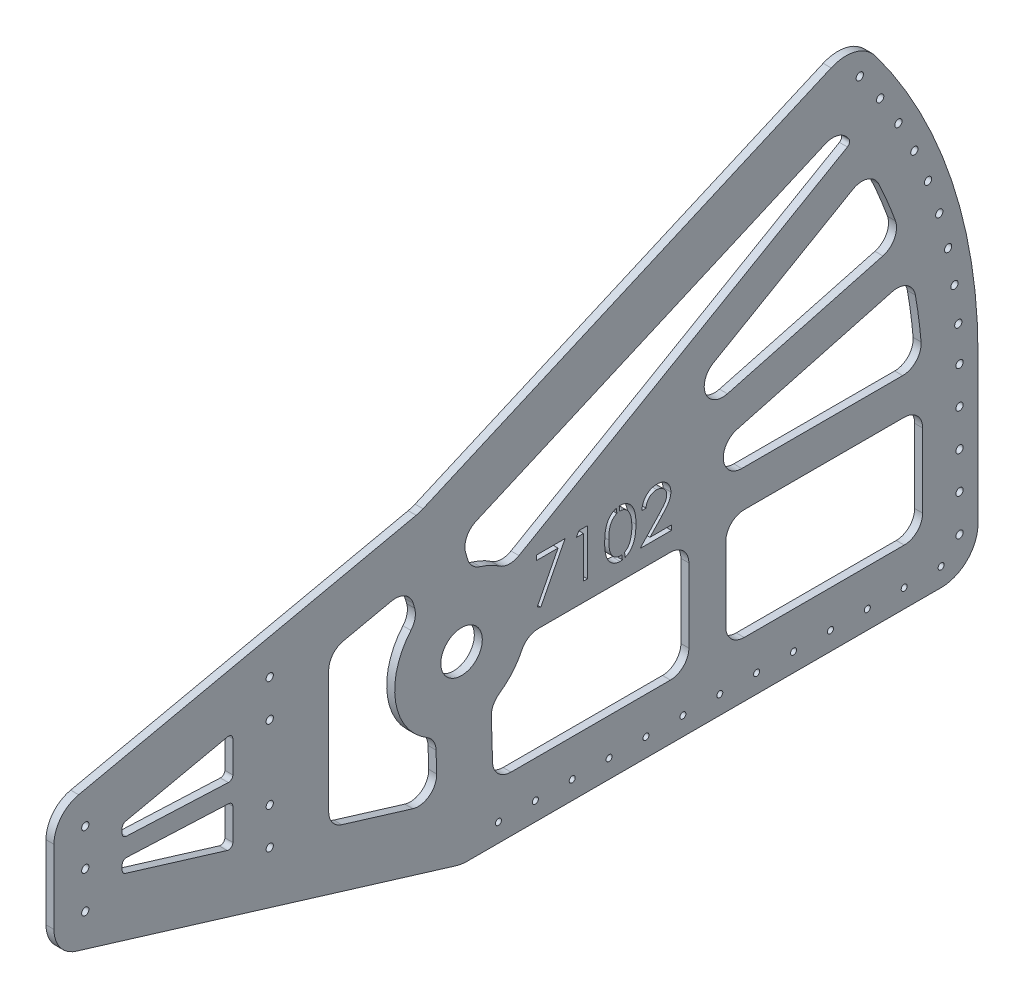
SolidWorks part; units mm, degrees
ref_plane "Front Plane" through (0, 0, 0) normal (0, 0, 1) x (1, 0, 0)
ref_plane "Top Plane" through (0, 0, 0) normal (0, 1, 0) x (1, 0, 0)
ref_plane "Right Plane" through (0, 0, 0) normal (1, 0, 0) x (0, 0, -1)
sketch "Sketch1" plane through (0, 0, 0) normal (1, 0, 0) x (0, 0, -1)
  line L0 (0, 0) -> (-195.58, 0) construction
  line L1 (7.3323, 0) -> (3.6662, 6.35) construction
  line L2 (3.6662, 6.35) -> (-3.6662, 6.35) construction
  line L3 (-3.6662, 6.35) -> (-7.3323, 0) construction
  line L4 (-7.3323, 0) -> (-3.6662, -6.35) construction
  line L5 (-3.6662, -6.35) -> (3.6662, -6.35) construction
  line L6 (3.6662, -6.35) -> (7.3323, 0) construction
  line L7 (0, -101.6) -> (0, -127) construction
  line L8 (-208.6619, 44.2059) -> (-28.8306, 97.4236)
  line L9 (0, -127) -> (-212.5477, -42.8649)
  line L10 (0, -127) -> (355.6, -127)
  line L11 (-28.8306, 97.4236) -> (272.3847, 228.6)
  line L12 (355.6, 0) -> (355.6, -127)
  circle A0 centre (0, 0) radius 76.2 construction
  circle A1 centre (0, 0) radius 14.2875
  circle A2 centre (0, 0) radius 6.35 construction
  circle A3 centre (0, 0) radius 33.4264 construction
  circle A4 centre (-195.58, 0) radius 9.906
  circle A5 centre (-195.58, 0) radius 25.4 construction
  circle A6 centre (-195.58, 25.4) radius 3.9687
  circle A7 centre (-170.18, 0) radius 3.9687
  circle A8 centre (-195.58, -25.4) radius 3.9688
  circle A9 centre (-220.98, 0) radius 3.9687
  circle A10 centre (-195.58, 0) radius 33.401 construction
  circle A11 centre (0, 0) radius 101.6
  circle A12 centre (-195.58, 0) radius 46.101
  circle A13 centre (215.9, 0) radius 114.3 construction
  arc A14 (304.8, -127) -> (248.0181, 217.9886) centre (0, 0) ccw
  arc A15 (355.6, 0) -> (272.3847, 228.6) centre (0, 0) ccw
  arc A16 (272.3847, 228.6) -> (332.1481, -127) centre (0, 0) ccw construction
  circle A17 centre (0, 0) radius 355.6 construction
  arc A18 (248.0181, 217.9886) -> (304.8, -127) centre (0, 0) ccw construction
  circle A19 centre (0, 0) radius 330.2 construction
  arc A22 (318.5144, -127) -> (260.2228, 223.3036) centre (0, 0) ccw
  arc A23 (260.2228, 223.3036) -> (318.5144, -127) centre (0, 0) ccw construction
  arc A24 (332.1481, -127) -> (355.6, 0) centre (0, 0) ccw construction
  point P26 (-195.58, 0)
  dimension "D1" = 152.4
  dimension "D2" = 28.575
  dimension "D4" = 66.8528
  dimension "D5" = 19.812
  dimension "D6" = 50.8
  dimension "D7" = 7.9375
  dimension "D11" = 66.802
  dimension "D14" = 228.6
  dimension "D17" = 355.6
  dimension "D18" = 25.4
  dimension "D19" = 685.8
  dimension "D3" = 12.7
  dimension "D9" = 195.58
  dimension "D13" = 25.4
  dimension "D16" = 355.6
  dimension "D10" = 25.4
  dimension "D12" = 12.7
  dimension "D15" = 25.4
  dimension "D8" = 4
extrude "Boss-Extrude1" add sketch "Sketch1" along normal mid plane 5.5 contours A12 A4 A6 A7 A8 A9 | A11 A1 | L10 A14 L11 A11 L8 A12 L9 | L10 A22 L11 A14 | A22 L10 L12 A15 L11 region at (0, 79.0972, -59.0807) region at (0, 18.9853, -149.0281) region at (0, 35.8903, 168.7722) region at (0, 217.3187, -255.5695) region at (0, 222.5763, -267.7737)
sketch "Sketch2" plane through (2.75, 0, 0) normal (1, 0, 0) x (0, 0, -1)
  line L0 (355.6, -114.3) -> (-32.0836, -114.3) construction
  line L1 (355.6, 0) -> (355.6, -127) construction
  line L2 (0, -127) -> (-212.5477, -42.8649) construction
  line L3 (0, -127) -> (355.6, -127) construction
  circle A0 centre (330.2, -114.3) radius 2.07
  circle A1 centre (304.8, -114.3) radius 2.07
  circle A2 centre (279.4, -114.3) radius 2.07
  circle A3 centre (254, -114.3) radius 2.07
  circle A4 centre (228.6, -114.3) radius 2.07
  circle A5 centre (203.2, -114.3) radius 2.07
  circle A6 centre (177.8, -114.3) radius 2.07
  circle A7 centre (152.4, -114.3) radius 2.07
  circle A8 centre (127, -114.3) radius 2.07
  circle A9 centre (101.6, -114.3) radius 2.07
  circle A10 centre (76.2, -114.3) radius 2.07
  circle A11 centre (50.8, -114.3) radius 2.07
  circle A12 centre (25.4, -114.3) radius 2.07
  dimension "D2" = 4.14
  dimension "D1" = 12.7
  dimension "D3" = 25.4
  dimension "D5" = 25.4
  dimension "D4" = 13
extrude "Cut-Extrude1" cut sketch "Sketch2" against normal up to next
sketch "Sketch3" plane through (2.75, 0, 0) normal (1, 0, 0) x (0, 0, -1)
  line L0 (342.9, 0) -> (342.9, -127) construction
  line L1 (0, -127) -> (355.6, -127) construction
  line L2 (0, 0) -> (342.9, 0) construction
  line L3 (0, 0) -> (342.0224, 24.5165) construction
  arc A0 (318.5144, -127) -> (260.2228, 223.3036) centre (0, 0) ccw construction
  arc A1 (342.9, 0) -> (260.2228, 223.3036) centre (0, 0) ccw construction
  arc A2 (318.5144, -127) -> (342.9, 0) centre (0, 0) ccw construction
  circle A3 centre (342.9, 0) radius 2.5
  circle A4 centre (342.0224, 24.5165) radius 2.5
  circle A5 centre (339.3943, 48.9075) radius 2.5
  circle A6 centre (335.0289, 73.0481) radius 2.5
  circle A7 centre (328.9488, 96.8149) radius 2.5
  circle A8 centre (321.1849, 120.0861) radius 2.5
  circle A9 centre (311.7771, 142.7427) radius 2.5
  circle A10 centre (300.7734, 164.6686) radius 2.5
  circle A11 centre (288.2303, 185.7517) radius 2.5
  circle A12 centre (274.2119, 205.8841) radius 2.5
  circle A13 centre (330.2, -114.3) radius 2.07 construction
  circle A14 centre (342.9, -25.4) radius 2.5
  circle A15 centre (342.9, -50.8) radius 2.5
  circle A16 centre (342.9, -76.2) radius 2.5
  circle A17 centre (342.9, -101.6) radius 2.5
  point P9 (0, 0)
  dimension "D1" = 5
  dimension "D3" = 342.9
  dimension "D4" = 4.1
  dimension "D6" = 25.4
  dimension "D5" = 5
  dimension "D2" = 10
extrude "Cut-Extrude2" cut sketch "Sketch3" against normal up to next
sketch "Sketch4" plane through (2.75, 0, 0) normal (1, 0, 0) x (0, 0, -1)
  line L0 (0, 0) -> (-195.58, 0) construction
  line L1 (0, 0) -> (-149.479, 0) construction
  line L2 (-195.58, 0) -> (-195.58, -49.5814) construction
  line L3 (0, -127) -> (-212.5477, -42.8649) construction
  line L4 (-280.63, 25.4) -> (-280.63, -25.4)
  line L5 (-265.3704, -46.0115) -> (0, -127)
  line L6 (-195.58, -49.5814) -> (-212.5477, -42.8649)
  line L7 (-263.6507, 46.4597) -> (-28.8306, 97.4236)
  line L8 (-208.6619, 44.2059) -> (-28.8306, 97.4236) construction
  line L9 (-208.6619, 44.2059) -> (-28.8306, 97.4236)
  line L10 (-149.479, 0) -> (-195.58, 0) construction
  line L11 (0, -127) -> (-195.58, -49.5814)
  circle A0 centre (-132.08, 25.4) radius 2.5
  circle A1 centre (-132.08, -25.4) radius 2.5
  circle A2 centre (-132.08, 0) radius 2.5
  circle A3 centre (-259.08, -25.4) radius 2.5
  circle A4 centre (-259.08, 0) radius 2.5
  circle A5 centre (-259.08, 25.4) radius 2.5
  arc A6 (-280.63, 25.4) -> (-263.6507, 46.4597) centre (-259.08, 25.4) cw
  arc A7 (-280.63, -25.4) -> (-265.3704, -46.0115) centre (-259.08, -25.4) ccw
  circle A8 centre (-195.58, 0) radius 46.101 construction
  arc A9 (-208.6619, 44.2059) -> (-212.5477, -42.8649) centre (-195.58, 0) ccw
  arc A10 (-149.479, 0) -> (-208.6619, 44.2059) centre (-195.58, 0) ccw construction
  arc A11 (-195.58, -46.101) -> (-149.479, 0) centre (-195.58, 0) ccw construction
  arc A12 (-212.5477, -42.8649) -> (-195.58, -46.101) centre (-195.58, 0) ccw construction
  arc A13 (-263.6507, 46.4597) -> (-280.63, 25.4) centre (-259.08, 25.4) cw construction
  circle A14 centre (-259.08, 25.4) radius 21.55 construction
  arc A15 (-265.3704, -46.0115) -> (-280.63, -25.4) centre (-259.08, -25.4) ccw construction
  circle A16 centre (-259.08, -25.4) radius 21.55 construction
  dimension "D1" = 5
  dimension "D2" = 25.4
  dimension "D3" = 63.5
  dimension "D4" = 19.05
extrude "Boss-Extrude2" add sketch "Sketch4" against normal up to surface (5.5 mm away) up to face at (-2.75, 24.5165, -344.5224)
extrude "Cut-Extrude3" cut sketch "Sketch4<2>" against normal up to next contours A0 | A1
sketch "Sketch4<2>" plane through (2.75, 0, 0) normal (1, 0, 0) x (0, 0, -1) same geometry as "Sketch4"
sketch "Sketch5" plane through (2.75, 0, 0) normal (1, 0, 0) x (0, 0, -1)
  line L0 (-132.08, 75.015) -> (-132.08, -86.6904) construction
  line L1 (-28.8306, 97.4236) -> (-263.6507, 46.4597) construction
  line L2 (-265.3704, -46.0115) -> (0, -127) construction
  line L3 (0, 0) -> (-195.58, 0) construction
  line L4 (0, 0) -> (-195.58, 0) construction
  circle A1 centre (-132.08, 25.4) radius 2.5 construction
  circle A2 centre (-132.08, 25.4) radius 2.5 construction
  circle A3 centre (-132.08, 50.8) radius 2.5
  circle A4 centre (-132.08, -50.8) radius 2.5
  dimension "D1" = 50.8
extrude "Cut-Extrude4" cut sketch "Sketch5" against normal up to next
fillet "Fillet1" radius 25.4 4 edges at (0, -127, 0) (0, -127, -355.6) (0, 228.6, -272.3847) (0, 97.4236, 28.8306)
sketch "Sketch9" plane through (2.75, 0, 0) normal (1, 0, 0) x (0, 0, -1)
  line L0 (-91.48, 50.8) -> (-91.48, -50.8)
  line L1 (-26.5293, 98.4258) -> (254.4732, 220.7998) construction
  line L2 (355.6, 0) -> (355.6, -101.6) construction
  line L3 (3.7896, -127) -> (330.2, -127) construction
  line L4 (-265.3704, -46.0115) -> (-3.6246, -125.8938) construction
  line L5 (-280.63, 25.4) -> (-280.63, -25.4) construction
  line L6 (-31.2836, 96.8912) -> (-263.6507, 46.4597) construction
  line L7 (355.6, 0) -> (355.6, -101.6)
  line L8 (3.7896, -127) -> (330.2, -127)
  line L9 (-265.3704, -46.0115) -> (-3.6246, -125.8938)
  line L10 (-280.63, 25.4) -> (-280.63, -25.4)
  line L11 (-31.2836, 96.8912) -> (-263.6507, 46.4597)
  line L12 (-26.5293, 98.4258) -> (254.4732, 220.7998)
  line L13 (0, 0) -> (-28.8687, 97.5413) construction
  line L14 (0, 0) -> (3.7896, -127) construction
  line L15 (18.9678, 3.0375) -> (22.8481, -127)
  line L16 (18.9678, 3.0375) -> (-11.2349, 105.0864)
  line L17 (-18.9678, -3.0375) -> (-15.2519, -127.5682)
  line L18 (-6.3726, -45.5943) -> (-47.5013, 93.3714)
  line L19 (-18.9678, -3.0375) -> (-47.1354, 92.135) construction
  line L20 (18.9678, 3.0375) -> (-10.6019, 102.9476) construction
  line L21 (18.9678, 3.0375) -> (22.8312, -126.4318) construction
  line L22 (-23.2028, 59.658) -> (-242.53, 12.0566)
  line L23 (-242.53, 12.0566) -> (-242.53, -13.1473)
  line L24 (-242.53, -13.1473) -> (5.6845, -88.9)
  line L25 (5.6845, -88.9) -> (317.5, -88.9)
  line L26 (317.5, 0) -> (317.5, -88.9)
  line L27 (-11.3171, 63.4945) -> (260.3085, 181.7848)
  circle A0 centre (-132.08, -50.8) radius 2.5 construction
  circle A1 centre (-132.08, 50.8) radius 2.5 construction
  circle A2 centre (0, 0) radius 46.0375
  circle A3 centre (0, 0) radius 46.0375
  circle A13 centre (-132.08, -50.8) radius 2.5
  circle A14 centre (-132.08, 50.8) radius 2.5
  circle A15 centre (-132.08, -50.8) radius 40.6
  circle A16 centre (-132.08, 50.8) radius 40.6
  arc A17 (284.9697, 212.7055) -> (254.4732, 220.7998) centre (264.6148, 197.5122) ccw construction
  arc A18 (355.6, 0) -> (284.9697, 212.7055) centre (0, 0) ccw construction
  arc A19 (330.2, -127) -> (355.6, -101.6) centre (330.2, -101.6) ccw construction
  arc A20 (-3.6246, -125.8938) -> (3.7896, -127) centre (3.7896, -101.6) ccw construction
  arc A21 (-280.63, -25.4) -> (-265.3704, -46.0115) centre (-259.08, -25.4) ccw construction
  arc A22 (-263.6507, 46.4597) -> (-280.63, 25.4) centre (-259.08, 25.4) ccw construction
  arc A23 (-31.2836, 96.8912) -> (-26.5293, 98.4258) centre (-36.6708, 121.7133) ccw construction
  arc A24 (284.9697, 212.7055) -> (254.4732, 220.7998) centre (264.6148, 197.5122) ccw
  arc A25 (355.6, 0) -> (284.9697, 212.7055) centre (0, 0) ccw
  arc A26 (330.2, -127) -> (355.6, -101.6) centre (330.2, -101.6) ccw
  arc A27 (-3.6246, -125.8938) -> (3.7896, -127) centre (3.7896, -101.6) ccw
  arc A28 (-280.63, -25.4) -> (-265.3704, -46.0115) centre (-259.08, -25.4) ccw
  arc A29 (-263.6507, 46.4597) -> (-280.63, 25.4) centre (-259.08, 25.4) ccw
  arc A30 (-31.2836, 96.8912) -> (-26.5293, 98.4258) centre (-36.6708, 121.7133) ccw
  arc A31 (-242.53, 12.0566) -> (-242.53, 12.0566) centre (-242.53, 12.0566) ccw
  arc A32 (-242.53, -13.1473) -> (-242.53, -13.1473) centre (-242.53, -13.1473) ccw
  arc A33 (5.6845, -88.9) -> (5.6845, -88.9) centre (5.6845, -88.9) ccw
  arc A34 (317.5, -88.9) -> (317.5, -88.9) centre (317.5, -88.9) ccw
  arc A35 (317.5, 0) -> (260.3085, 181.7848) centre (0, 0) ccw
  arc A36 (260.3085, 181.7848) -> (260.3085, 181.7848) centre (260.3085, 181.7848) ccw
  arc A37 (-23.2028, 59.658) -> (-11.3171, 63.4945) centre (-36.6708, 121.7133) ccw
  dimension "D1" = 31.75
  dimension "D2" = 38.1
  dimension "D3" = 19.05
  dimension "D4" = 19.05
  dimension "D5" = 38.1
extrude "Cut-Extrude7" cut sketch "Sketch9" against normal through all contours A16 L0 A15 L24 L17 A3 L18 L22 | A35 A36 L27 L16 A3 L15 L25 A34 L26 region at (2.75, -14.028, 59.5734) region at (2.75, 23.1221, -177.6674)
fillet "Fillet2" radius 12.7 12 edges at (0, -88.9, -317.5) (0, -88.9, -21.7112) (0, -41.3244, -20.2916) (0, 45.5943, -6.3726) (0, 68.2749, 0.34) (0, 181.7848, -260.3085) (0, 44.8396, 91.48) (0, 56.7376, 36.6591) (0, 34.7817, 30.1609) (0, -42.4607, 17.7915) (0, -82.0963, 16.6088) (0, -58.9915, 92.315)
sketch "Sketch10" plane through (2.75, 0, 0) normal (1, 0, 0) x (0, 0, -1)
  line L0 (0, 0) -> (274.9631, 158.75) construction
  line L1 (0, 0) -> (317.5, 0) construction
  line L2 (317.5, 0) -> (317.5, -76.2) construction
  line L4 (0, 0) -> (306.6814, 82.175) construction
  line L5 (6.35, -10.9985) -> (281.3131, 147.7515)
  line L6 (0, -12.7) -> (317.5, -12.7)
  line L7 (3.287, -12.2673) -> (309.9685, 69.9078)
  line L8 (-6.35, 10.9985) -> (268.6131, 169.7485)
  line L9 (0, 12.7) -> (317.5, 12.7)
  line L10 (-3.287, 12.2673) -> (303.3944, 94.4423)
  line L11 (20.9295, -62.7028) -> (317.5, -62.7028) construction
  line L12 (20.5155, -48.8267) -> (21.3436, -76.5788) construction
  line L13 (169.2148, -88.9) -> (169.2148, -12.7) construction
  line L15 (181.9148, -88.9) -> (181.9148, -12.7)
  line L16 (156.5148, -88.9) -> (156.5148, -12.7)
  line L17 (34.0379, -88.9) -> (304.8, -88.9) construction
  line L18 (4.2425, 52.7914) -> (2.8461, 57.5095) construction
  line L19 (9.9532, 72.7575) -> (250.6127, 177.5624) construction
  line L20 (317.5, 0) -> (317.5, -76.2)
  line L21 (34.0379, -88.9) -> (304.8, -88.9)
  line L22 (20.5155, -48.8267) -> (21.3436, -76.5788)
  line L23 (4.2425, 52.7914) -> (2.8461, 57.5095)
  line L24 (9.9532, 72.7575) -> (250.6127, 177.5624)
  arc A1 (317.5, 0) -> (266.337, 172.8319) centre (0, 0) ccw construction
  arc A2 (266.337, 172.8319) -> (250.6127, 177.5624) centre (255.6835, 165.9186) ccw construction
  arc A3 (304.8, -88.9) -> (317.5, -76.2) centre (304.8, -76.2) ccw construction
  arc A4 (21.3436, -76.5788) -> (34.0379, -88.9) centre (34.0379, -76.2) ccw construction
  arc A5 (26.0293, -37.9727) -> (20.5155, -48.8267) centre (33.2098, -48.4479) ccw construction
  arc A6 (26.0293, -37.9727) -> (12.87, 44.202) centre (0, 0) ccw construction
  arc A7 (4.2425, 52.7914) -> (12.87, 44.202) centre (16.4203, 56.3956) ccw construction
  arc A8 (9.9532, 72.7575) -> (2.8461, 57.5095) centre (15.024, 61.1137) ccw construction
  arc A9 (266.337, 172.8319) -> (250.6127, 177.5624) centre (255.6835, 165.9186) ccw
  arc A10 (317.5, 0) -> (266.337, 172.8319) centre (0, 0) ccw
  arc A11 (304.8, -88.9) -> (317.5, -76.2) centre (304.8, -76.2) ccw
  arc A12 (21.3436, -76.5788) -> (34.0379, -88.9) centre (34.0379, -76.2) ccw
  arc A13 (26.0293, -37.9727) -> (20.5155, -48.8267) centre (33.2098, -48.4479) ccw
  arc A14 (26.0293, -37.9727) -> (12.87, 44.202) centre (0, 0) ccw
  arc A15 (4.2425, 52.7914) -> (12.87, 44.202) centre (16.4203, 56.3956) ccw
  arc A16 (9.9532, 72.7575) -> (2.8461, 57.5095) centre (15.024, 61.1137) ccw
  point P32 (169.2148, -62.7028)
  dimension "D1" = 30
  dimension "D2" = 15
  dimension "D3" = 12.7
  dimension "D4" = 12.7
  dimension "D5" = 12.7
  dimension "D6" = 12.7
extrude "Boss-Extrude3" add sketch "Sketch10" against normal up to surface (5.5 mm away) contours A14 L10 L5 A10 L8 | A14 L9 L5 L10 | L7 A10 L10 L5 L9 | A14 L6 L20 A10 L9 L7 | L16 L21 L15 L6 | A14 L7 L9 L5 | A14 L5 L9 region at (2.75, 12.1765, -45.4433) region at (2.75, 8.1966, -62.5947) region at (2.75, 24.1989, -58.3069) region at (2.75, 50.3944, -188.0743) region at (2.75, -0.4381, -187.7663) region at (2.75, 94.2506, -162.3737) region at (2.75, -50.8, -169.2148) up to face at (-2.75, 12.8289, -124.8269)
fillet "Fillet3" radius 12.7 13 edges at (0, 12.7, -317.2459) (0, 12.7, -96.4661) (0, 69.842, -309.723) (0, 94.3765, -303.149) (0, 37.2345, -89.8921) (0, -12.7, -44.2511) (0, -12.7, -156.5148) (0, -88.9, -156.5148) (0, -88.9, -181.9148) (0, -12.7, -181.9148) (0, -12.7, -317.5) (0, 147.6244, -281.093) (0, 33.1241, -31.9726)
fillet "Fillet4" radius 3 1 edges at (0, 169.6215, -268.393)
sketch "Sketch11" plane through (2.75, 0, 0) normal (1, 0, 0) x (0, 0, -1)
  line L0 (14.2875, 0) -> (180.3408, 0) construction
  circle A0 centre (0, 0) radius 14.2875 construction
  arc A2 (189.6452, 37.6673) -> (192.9322, 12.7) centre (192.9322, 25.4) ccw construction
  text T0 "7102" font "Century Gothic" height 31.75
  point P11 (180.3408, 23.7423)
extrude "Cut-Extrude8" cut sketch "Sketch11" against normal through all both and the other way through all
sketch "Sketch12" plane through (2.75, 0, 0) normal (1, 0, 0) x (0, 0, -1)
  line L0 (106.2944, 42.1551) -> (113.1249, -11.5436) construction
  line L1 (105.3023, 42.0289) -> (112.1329, -11.6698)
  line L2 (107.2864, 42.2813) -> (114.1169, -11.4174)
  line L3 (107.2864, 42.2813) -> (105.3023, 42.0289)
  line L4 (114.1169, -11.4174) -> (112.1329, -11.6698)
  dimension "D1" = 1
  dimension "D2" = 1
extrude "Boss-Extrude4" add sketch "Sketch12" against normal up to surface (5.5 mm away) up to face at (-2.75, 20.0812, -83.5136)
sketch "Sketch14" plane through (2.75, 0, 0) normal (1, 0, 0) x (0, 0, -1)
  circle A0 centre (-195.58, 0) radius 29.3688
extrude "Boss-Extrude6" add sketch "Sketch14" against normal up to surface (5.5 mm away) up to face at (-2.75, 18.853, -112.6454)
sketch "Sketch15" plane through (2.75, 0, 0) normal (1, 0, 0) x (0, 0, -1)
  line L0 (-242.53, -13.1473) -> (5.6845, -88.9)
  line L1 (5.6845, -88.9) -> (317.5, -88.9)
  line L2 (317.5, -88.9) -> (317.5, 0)
  line L3 (260.3085, 181.7848) -> (-11.3171, 63.4945)
  line L4 (-23.2028, 59.658) -> (-242.53, 12.0566)
  line L5 (-242.53, 12.0566) -> (-242.53, -13.1473)
  line L6 (-265.3704, -46.0115) -> (-3.6246, -125.8938)
  line L7 (3.7896, -127) -> (330.2, -127)
  line L8 (355.6, -101.6) -> (355.6, 0)
  line L9 (254.4732, 220.7998) -> (-26.5293, 98.4258)
  line L10 (-31.2836, 96.8912) -> (-263.6507, 46.4597)
  line L11 (-280.63, 25.4) -> (-280.63, -25.4)
  line L12 (-265.3704, -46.0115) -> (-3.6246, -125.8938)
  line L13 (3.7896, -127) -> (330.2, -127)
  line L14 (355.6, -101.6) -> (355.6, 0)
  line L15 (254.4732, 220.7998) -> (-26.5293, 98.4258)
  line L16 (-31.2836, 96.8912) -> (-263.6507, 46.4597)
  line L17 (-280.63, 25.4) -> (-280.63, -25.4)
  line L18 (-157.48, 30.5153) -> (-157.48, -39.1038)
  line L19 (-233.68, 13.9774) -> (-233.68, -15.8483)
  line L20 (-233.68, -0.9354) -> (-157.48, -4.2942)
  line L21 (-280.63, -5.2221) -> (-157.48, -10.6504)
  line L22 (-233.68, 5.4207) -> (-157.2004, 2.0496)
  line L23 (-233.4004, 5.4084) -> (-157.2004, 2.0496) construction
  line L24 (-233.9596, -7.2793) -> (-157.7596, -10.6381) construction
  arc A0 (5.6845, -88.9) -> (5.6845, -88.9) centre (5.6845, -88.9) ccw
  arc A1 (317.5, -88.9) -> (317.5, -88.9) centre (317.5, -88.9) ccw
  arc A2 (317.5, 0) -> (260.3085, 181.7848) centre (0, 0) ccw
  arc A3 (260.3085, 181.7848) -> (260.3085, 181.7848) centre (260.3085, 181.7848) ccw
  arc A4 (-23.2028, 59.658) -> (-11.3171, 63.4945) centre (-36.6708, 121.7133) ccw
  arc A5 (-242.53, 12.0566) -> (-242.53, 12.0566) centre (-242.53, 12.0566) ccw
  arc A6 (-242.53, -13.1473) -> (-242.53, -13.1473) centre (-242.53, -13.1473) ccw
  arc A7 (-3.6246, -125.8938) -> (3.7896, -127) centre (3.7896, -101.6) ccw
  arc A8 (330.2, -127) -> (355.6, -101.6) centre (330.2, -101.6) ccw
  arc A9 (355.6, 0) -> (284.9697, 212.7055) centre (0, 0) ccw
  arc A10 (284.9697, 212.7055) -> (254.4732, 220.7998) centre (264.6148, 197.5122) ccw
  arc A11 (-31.2836, 96.8912) -> (-26.5293, 98.4258) centre (-36.6708, 121.7133) ccw
  arc A12 (-263.6507, 46.4597) -> (-280.63, 25.4) centre (-259.08, 25.4) ccw
  arc A13 (-280.63, -25.4) -> (-265.3704, -46.0115) centre (-259.08, -25.4) ccw
  arc A14 (-3.6246, -125.8938) -> (3.7896, -127) centre (3.7896, -101.6) ccw
  arc A15 (330.2, -127) -> (355.6, -101.6) centre (330.2, -101.6) ccw
  arc A16 (355.6, 0) -> (284.9697, 212.7055) centre (0, 0) ccw
  arc A17 (284.9697, 212.7055) -> (254.4732, 220.7998) centre (264.6148, 197.5122) ccw
  arc A18 (-31.2836, 96.8912) -> (-26.5293, 98.4258) centre (-36.6708, 121.7133) ccw
  arc A19 (-263.6507, 46.4597) -> (-280.63, 25.4) centre (-259.08, 25.4) ccw
  arc A20 (-280.63, -25.4) -> (-265.3704, -46.0115) centre (-259.08, -25.4) ccw
  circle A21 centre (-132.08, 25.4) radius 2.5 construction
  circle A22 centre (-259.08, 0) radius 2.5 construction
  dimension "D4" = 25.4
  dimension "D3" = 25.4
  dimension "D1" = 0
  dimension "D2" = 38.1
  dimension "D5" = 6.35
  dimension "D6" = 6.35
extrude "Cut-Extrude9" cut sketch "Sketch15" against normal through all both and the other way through all contours L21 L19 L0 L18 | L19 L22 L18 L4 region at (2.75, -19.4158, 188.7524) region at (2.75, 13.5843, 188.7524)
fillet "Fillet5" radius 3 8 edges at (0, -10.6504, 157.48) (0, -39.1038, 157.48) (0, -15.8483, 233.68) (0, -7.2916, 233.68) (0, 30.5153, 157.48) (0, 2.0619, 157.48) (0, 5.4207, 233.68) (0, 13.9774, 233.68)
